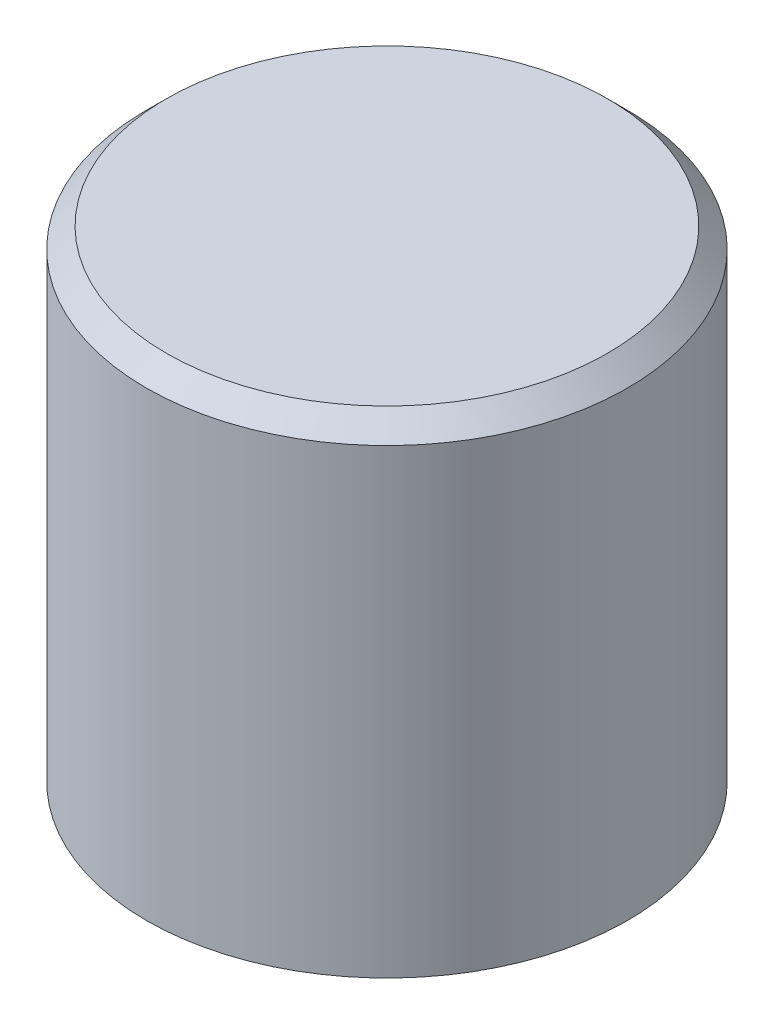
SolidWorks part; units mm, degrees
ref_plane "Front Plane" through (0, 0, 0) normal (0, 0, 1) x (1, 0, 0)
ref_plane "Top Plane" through (0, 0, 0) normal (0, 1, 0) x (1, 0, 0)
ref_plane "Right Plane" through (0, 0, 0) normal (1, 0, 0) x (0, 0, -1)
sketch "Sketch1" plane through (0, 0, 0) normal (0, 0, 1) x (1, 0, 0)
  line L0 (0, 0) -> (0, -7113.7616) construction
  line L1 (0, 0) -> (7113.7616, 0) construction
  line L2 (0, 12) -> (-6, 12)
  line L4 (-6, 12) -> (-6, 0)
  line L5 (-6, 0) -> (-5, 0)
  line L6 (-5, 0) -> (-5, 3)
  line L7 (-5, 3) -> (-1.5, 3.6171)
  line L8 (-1.5, 3.6171) -> (-1.5, 8.5)
  line L9 (-1.5, 8.5) -> (0, 8.5)
  line L10 (0, 12) -> (0, 8.5)
  point P7 (-6, 12)
  point P12 (0, 0)
  dimension "D1" = 12
  dimension "D2" = 3
  dimension "D3" = 100
  dimension "D4" = 8.5
  dimension "D6" = 10
  dimension "D7" = 3
  dimension "D8" = 12
revolve "Revolve2" add sketch "Sketch1" angle 360 about L0
chamfer "Chamfer1" distance 0.5 angle 45 1 edges at (0, 12, 6)
chamfer "Chamfer2" distance 0.1 angle 45 1 edges at (0, 3.6171, 1.5) first distance on face at (0, 8.5, 1.5)
